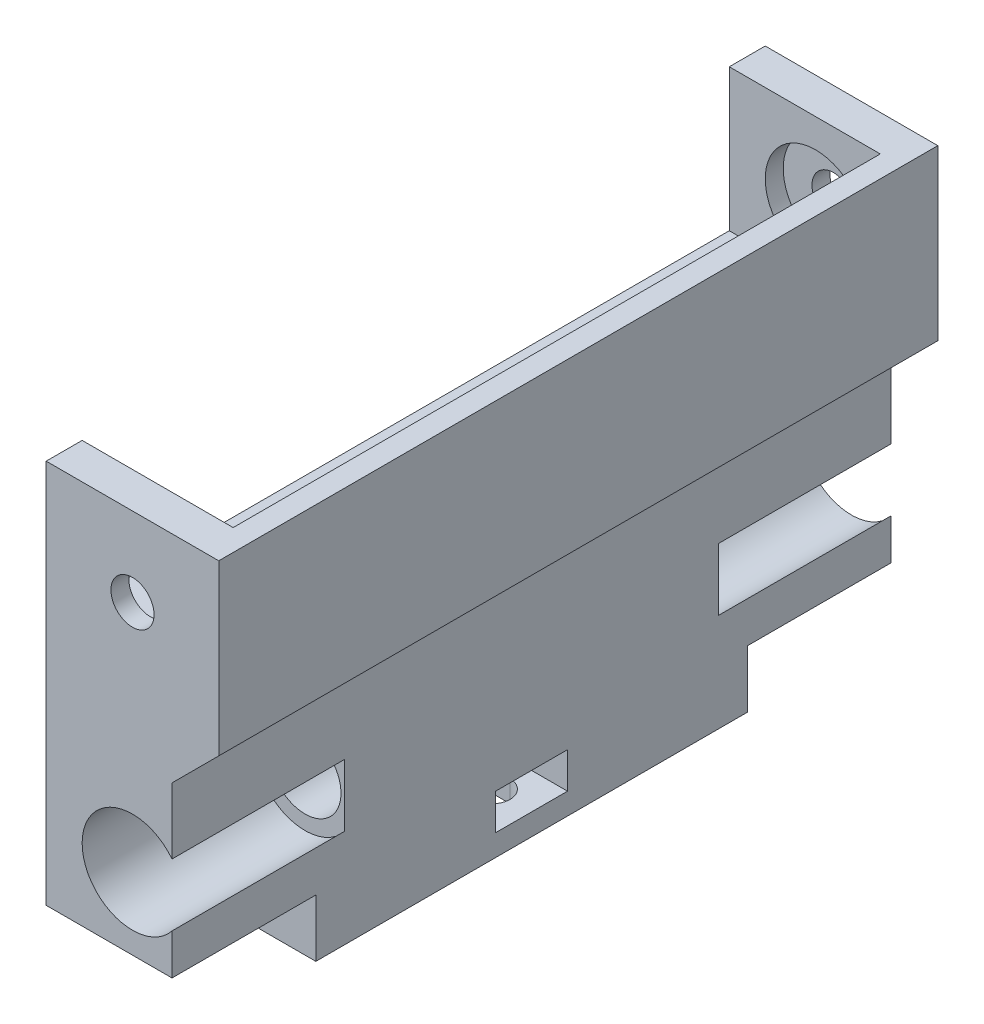
SolidWorks part; units mm, degrees
ref_plane "Front Plane" through (0, 0, 0) normal (0, 0, 1) x (1, 0, 0)
ref_plane "Top Plane" through (0, 0, 0) normal (0, 1, 0) x (1, 0, 0)
ref_plane "Right Plane" through (0, 0, 0) normal (1, 0, 0) x (0, 0, -1)
sketch "Sketch1" plane through (0, 0, 0) normal (0, 0, 1) x (1, 0, 0)
  line L0 (-12, 7) -> (9, 7)
  line L1 (-12, 26.75) -> (12, 26.75) construction
  line L2 (-12, 26.75) -> (-12, -26.75) construction
  line L3 (-12, -26.75) -> (12, -26.75)
  line L4 (12, 26.75) -> (12, -26.75)
  line L5 (-12, 26.75) -> (12, -26.75) construction
  line L6 (-12, -26.75) -> (12, 26.75) construction
  line L7 (9, 7) -> (9, 26.75)
  line L8 (9, 26.75) -> (12, 26.75)
  line L9 (-12, 7) -> (-12, -26.75)
  line L10 (-12, 7.75) -> (-12, 6.25) construction
  circle A0 centre (0, -16.75) radius 7
  circle A1 centre (-12, -0.75) radius 7 construction
  circle A2 centre (-12, 15.75) radius 8 construction
  point P2 (-7, -16.75)
  point P4 (0, 0)
  point P9 (0, -23.75)
  point P14 (-12, 7.75)
  point P15 (0, -9.75)
  point P16 (-12, -7.75)
  point P17 (-12, 23.75)
  dimension "D1" = 14
  dimension "D5" = 16
  dimension "D2" = 5
  dimension "D3" = 3
  dimension "D4" = 8.5
  dimension "D6" = 2
  dimension "D7" = 3
  dimension "D8" = 3
extrude "Boss-Extrude1" add sketch "Sketch1" along normal mid plane 100
sketch "Sketch2" plane through (-12, 0, 0) normal (-1, 0, 0) x (0, 0, 1)
  line L0 (-24.1, -0.75) -> (24.1, -0.75) construction
  circle A0 centre (-24.1, -0.75) radius 4
  circle A1 centre (24.1, -0.75) radius 4
  point P0 (0, -0.75)
  dimension "D2" = 8
  dimension "D1" = 48.2
extrude "Cut-Extrude1" cut sketch "Sketch2" against normal offset from surface (17 mm away) 7 up to face at (12, 0, 0)
sketch "Sketch3" plane through (9, 0, 0) normal (-1, 0, 0) x (0, 0, 1)
  line L0 (50, 7) -> (-50, 7) construction
  line L1 (-50, 26.75) -> (-45, 26.75)
  line L2 (-50, 26.75) -> (-50, 7)
  line L3 (-50, 7) -> (-45, 7)
  line L4 (-45, 26.75) -> (-45, 7)
  line L6 (50, 26.75) -> (45, 26.75)
  line L7 (50, 26.75) -> (50, 7)
  line L8 (50, 7) -> (45, 7)
  line L9 (45, 26.75) -> (45, 7)
  dimension "D1" = 5
extrude "Boss-Extrude2" add sketch "Sketch3" along normal through all
sketch "Sketch4" plane through (0, 0, 0) normal (0, 0, 1) x (1, 0, 0)
  circle A0 centre (0, 15.75) radius 7
  dimension "D1" = 14
extrude "Cut-Extrude4" cut sketch "Sketch4" against normal mid plane 95
sketch "Sketch6" plane through (0, 0, 0) normal (0, 0, 1) x (1, 0, 0)
  circle A0 centre (0, -16.75) radius 5
  circle A1 centre (0, -16.75) radius 7 construction
  circle A2 centre (0, -16.75) radius 7
  dimension "D1" = 10
extrude "Boss-Extrude3" add sketch "Sketch6" along normal mid plane 52
sketch "Sketch7" plane through (-12, 0, 0) normal (-1, 0, 0) x (0, 0, 1)
  line L0 (-35, -16.75) -> (35, -16.75) construction
  circle A0 centre (-35, -16.75) radius 1
  circle A1 centre (35, -16.75) radius 1
  dimension "D1" = 2
  dimension "D2" = 70
extrude "Cut-Extrude5" cut sketch "Sketch7" against normal up to next
sketch "Sketch8" plane through (0, 0, 47.5) normal (0, 0, -1) x (-1, 0, 0)
  circle A0 centre (0, 15.75) radius 3
  dimension "D1" = 6
extrude "Cut-Extrude6" cut sketch "Sketch8" against normal through all both and the other way through all
sketch "Sketch9" plane through (0, 0, 50) normal (0, 0, 1) x (1, 0, 0)
  line L0 (5.5, -3.25) -> (12, 3.25)
  line L1 (12, -26.75) -> (5.5, -26.75)
  line L2 (12, -26.75) -> (12, 3.25)
  line L4 (5.5, -26.75) -> (5.5, -3.25)
  circle A0 centre (0, -16.75) radius 7 construction
  circle A1 centre (0, -16.75) radius 7 construction
  point P5 (7, -16.75)
  dimension "D1" = 1.5
  dimension "D2" = 30
  dimension "D3" = 45
extrude "Cut-Extrude7" cut sketch "Sketch9" against normal through all
sketch "Sketch10" plane through (-12, 0, 0) normal (-1, 0, 0) x (0, 0, 1)
  line L0 (-5, -26.75) -> (-5, -31.75)
  line L1 (50, -26.75) -> (-50, -26.75) construction
  line L2 (-5, -31.75) -> (5, -31.75)
  line L3 (5, -31.75) -> (5, -26.75)
  line L4 (5, -26.75) -> (30, -26.75)
  line L5 (30, -26.75) -> (30, -34.75)
  line L6 (30, -34.75) -> (-30, -34.75)
  line L7 (-30, -34.75) -> (-30, -26.75)
  line L8 (-30, -26.75) -> (-5, -26.75)
  line L9 (-50, 26.75) -> (-50, -26.75) construction
  point P15 (0, -31.75)
  dimension "D1" = 5
  dimension "D2" = 3
  dimension "D3" = 10
  dimension "D4" = 20
extrude "Boss-Extrude4" add sketch "Sketch10" against normal up to surface (17.5 mm away) up to face at (5.5, -16.1667, 0)
sketch "Sketch11" plane through (0, -31.75, 0) normal (0, 1, 0) x (1, 0, 0)
  line L0 (0, 2.5) -> (-12, 2.5)
  line L1 (-12, -5) -> (-12, 5) construction
  line L2 (-12, 2.5) -> (-12, -2.5)
  line L3 (-12, -2.5) -> (0, -2.5)
  line L5 (-5, -26) -> (5, -26) construction
  line L6 (-5, -26) -> (5, -26) construction
  arc A0 (0, 2.5) -> (0, -2.5) centre (0, 0) cw
  point P16 (0, -26)
  dimension "D1" = 5
extrude "Cut-Extrude8" cut sketch "Sketch11" against normal through all
sketch "Sketch12" [suppressed] plane through (0, 7, 0) normal (0, 1, 0) x (1, 0, 0)
  line L0 (2, 12.55) -> (-2, 12.55) construction
  line L1 (2, 18.1) -> (7, 18.1)
  line L2 (2, 18.1) -> (2, 7)
  line L3 (2, 7) -> (7, 7)
  line L4 (7, 18.1) -> (7, 7)
  line L5 (-2, 18.1) -> (-7, 18.1)
  line L6 (-2, 18.1) -> (-2, 7)
  line L7 (-2, 7) -> (-7, 7)
  line L8 (-7, 18.1) -> (-7, 7)
  line L9 (-12, 20.1) -> (5, 20.1) construction
  line L10 (5.5, 5) -> (-12, 5) construction
  point P10 (0, 12.55)
  dimension "D1" = 2
  dimension "D2" = 2
  dimension "D3" = 4
  dimension "D4" = 14
extrude "Cut-Extrude9" [suppressed] cut sketch "Sketch12" against normal through all
sketch "Sketch13" [suppressed] plane through (0, -34.75, 0) normal (0, -1, 0) x (1, 0, 0)
  line L12 (5.5, -7) -> (12, -7)
  line L13 (12, -50) -> (12, 50) construction
  line L14 (12, -7) -> (12, -2.5)
  line L15 (12, -2.5) -> (5.5, -2.5)
  line L16 (5.5, 50) -> (5.5, -7) construction
  line L17 (5.5, -2.5) -> (5.5, -7)
  line L18 (0, -2.5) -> (-12, -2.5) construction
extrude "Boss-Extrude5" [suppressed] add sketch "Sketch13" against normal up to next
sketch "Sketch14" [suppressed] plane through (5.5, 0, 0) normal (-1, 0, 0) x (0, 0, 1)
  line L4 (-2.5, -26.75) -> (-5, -26.75)
  line L5 (-5, -26.75) -> (-5, -31.75)
  line L6 (-5, -31.75) -> (-2.5, -31.75)
  line L7 (-2.5, -31.75) -> (-2.5, -26.75)
  line L12 (-2.5, -26.75) -> (-5, -26.75)
  line L13 (-5, -26.75) -> (-5, -31.75)
  line L14 (-5, -31.75) -> (-2.5, -31.75)
  line L15 (-2.5, -31.75) -> (-2.5, -26.75)
  dimension "D1" = 0
extrude "Cut-Extrude10" [suppressed] cut sketch "Sketch14" against normal through all
sketch "Sketch16" [suppressed] plane through (0, 0, -7) normal (0, 0, -1) x (-1, 0, 0)
  line L0 (-12, -34.75) -> (-5, -34.75)
  line L1 (-2, -34.75) -> (-12, -34.75) construction
  line L2 (-5, -34.75) -> (-5, -49.75)
  line L3 (-5, -49.75) -> (5, -49.75)
  line L4 (5, -49.75) -> (5, -34.75)
  line L5 (-5.5, -34.75) -> (12, -34.75) construction
  line L6 (5, -34.75) -> (12, -34.75)
  line L7 (12, -34.75) -> (12, -51.75)
  line L9 (-12, -51.75) -> (-12, -34.75)
  line L10 (-12, -51.75) -> (-21, -51.75)
  line L11 (-21, -51.75) -> (-21, -93.75)
  line L12 (-21, -93.75) -> (21, -93.75)
  line L13 (21, -93.75) -> (21, -51.75)
  line L14 (21, -51.75) -> (12, -51.75)
  line L16 (-15.5, -88.25) -> (15.5, -88.25) construction
  line L17 (-15.5, -88.25) -> (-15.5, -57.25) construction
  line L18 (-15.5, -57.25) -> (15.5, -57.25) construction
  line L19 (15.5, -88.25) -> (15.5, -57.25) construction
  line L20 (-15.5, -88.25) -> (15.5, -57.25) construction
  line L21 (-15.5, -57.25) -> (15.5, -88.25) construction
  circle A0 centre (0, -72.75) radius 12.5
  circle A1 centre (-15.5, -57.25) radius 1.5
  circle A2 centre (15.5, -57.25) radius 1.5
  circle A3 centre (15.5, -88.25) radius 1.5
  circle A4 centre (-15.5, -88.25) radius 1.5
  point P20 (-21, -72.75)
  point P21 (0, -93.75)
  dimension "D5" = 25
  dimension "D7" = 3
  dimension "D1" = 10
  dimension "D2" = 15
  dimension "D3" = 2
  dimension "D4" = 42
  dimension "D6" = 31
extrude "Boss-Extrude8" [suppressed] add sketch "Sketch16" against normal up to surface (4.5 mm away) up to face at (-6, -33.25, -2.5)
sketch "Sketch18" [suppressed] plane through (12, 0, 0) normal (1, 0, 0) x (0, 0, -1)
  line L0 (2.5, -51.75) -> (-48.3, -51.75)
  line L1 (2.5, -51.75) -> (2.5, -31.75)
  line L2 (2.5, -31.75) -> (-5, -31.75)
  line L3 (-5, -31.75) -> (-5, -26.75)
  line L4 (-5, -26.75) -> (2.5, -26.75)
  line L5 (2.5, -26.75) -> (2.5, -7.3)
  line L6 (2.5, -3.25) -> (2.5, -26.75) construction
  line L7 (2.5, -7.3) -> (-48.3, -7.3)
  line L8 (-48.3, -7.3) -> (-48.3, -51.75)
  line L10 (-44.81, -47.94) -> (-0.99, -47.94) construction
  line L11 (-44.81, -47.94) -> (-44.81, -11.11) construction
  line L12 (-44.81, -11.11) -> (-0.99, -11.11) construction
  line L13 (-0.99, -47.94) -> (-0.99, -11.11) construction
  line L14 (-44.81, -47.94) -> (-0.99, -11.11) construction
  line L15 (-44.81, -11.11) -> (-0.99, -47.94) construction
  circle A0 centre (-44.81, -11.11) radius 1.375
  circle A2 centre (-0.99, -47.94) radius 1.375
  circle A3 centre (-44.81, -47.94) radius 1.375
  circle A4 centre (-1.63, -11.11) radius 1.375
  point P15 (-22.9, -29.525)
  point P21 (-48.3, -29.525)
  point P23 (-22.9, -51.75)
  dimension "D5" = 2.75
  dimension "D1" = 50.8
  dimension "D2" = 44.45
  dimension "D3" = 43.82
  dimension "D4" = 36.83
  dimension "D6" = 0.64
extrude "Boss-Extrude9" [suppressed] add sketch "Sketch18" against normal blind 2
sketch "Sketch20" [suppressed] plane through (10, 0, 0) normal (-1, 0, 0) x (0, 0, 1)
  line L0 (-2.5, -31.75) -> (-2.5, -34.75)
  line L1 (-2.5, -51.75) -> (-2.5, -31.75) construction
  line L3 (48.3, -7.3) -> (48.3, -51.75) construction
  line L5 (48.3, -21.0801) -> (-2.5, -21.0801)
  line L6 (-2.5, -21.0801) -> (-2.5, -26.75)
  line L7 (-2.5, -26.75) -> (5, -26.75)
  line L8 (5, -26.75) -> (5, -31.75)
  line L9 (5, -31.75) -> (-2.5, -31.75)
  line L10 (48.3, -21.0801) -> (48.3, -26.75)
  line L11 (48.3, -26.75) -> (30, -26.75)
  line L12 (30, -26.75) -> (30, -34.75)
  line L13 (30, -34.75) -> (-2.5, -34.75)
extrude "Boss-Extrude10" [suppressed] add sketch "Sketch20" along normal up to next
